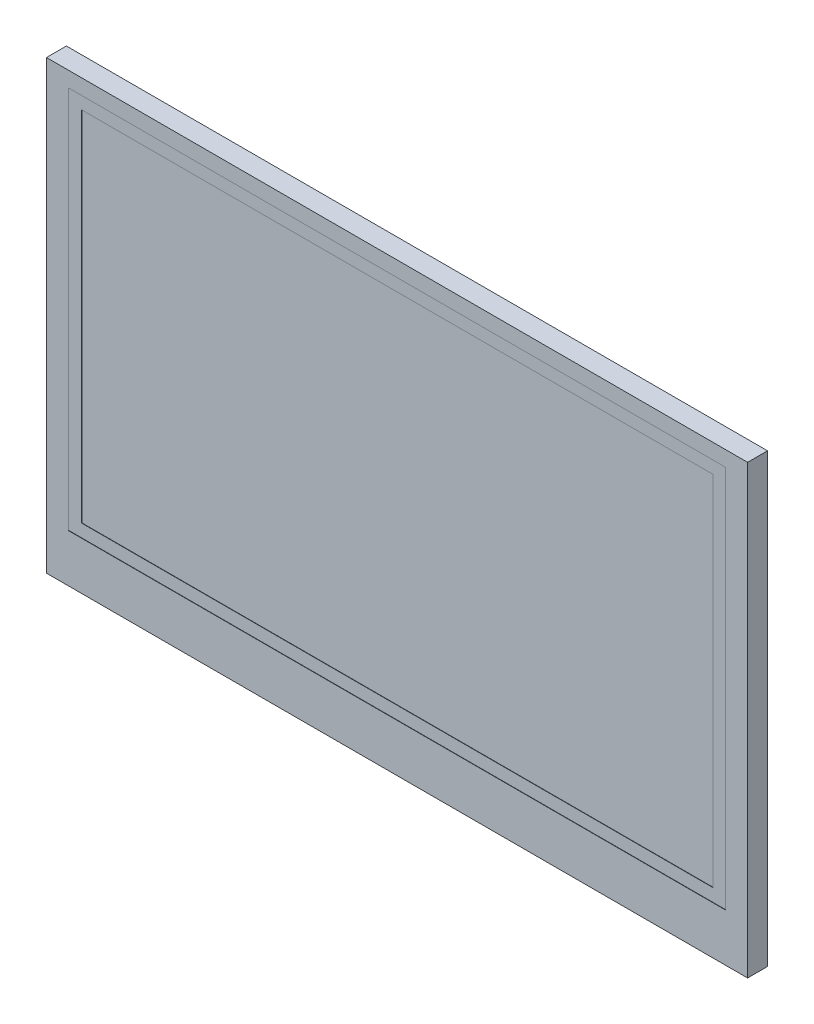
SolidWorks part; units mm, degrees
ref_plane "Front Plane" through (0, 0, 0) normal (0, 0, 1) x (1, 0, 0)
ref_plane "Top Plane" through (0, 0, 0) normal (0, 1, 0) x (1, 0, 0)
ref_plane "Right Plane" through (0, 0, 0) normal (1, 0, 0) x (0, 0, -1)
sketch "Sketch1" plane through (0, 0, 0) normal (0, 0, 1) x (1, 0, 0)
  line L1 (52.75, 33.6) -> (-52.75, 33.6)
  line L2 (52.75, 33.6) -> (52.75, -33.6)
  line L3 (52.75, -33.6) -> (-52.75, -33.6)
  line L4 (-52.75, 33.6) -> (-52.75, -33.6)
  line L5 (52.75, 33.6) -> (-52.75, -33.6) construction
  line L6 (52.75, -33.6) -> (-52.75, 33.6) construction
  line L7 (-49.45, 31.3) -> (49.45, 31.3)
  line L8 (-49.45, 31.3) -> (-49.45, -26.4)
  line L9 (-49.45, -26.4) -> (49.45, -26.4)
  line L10 (49.45, 31.3) -> (49.45, -26.4)
  line L11 (-47.52, 29.38) -> (47.52, 29.38)
  line L12 (-47.52, 29.38) -> (-47.52, -24.476)
  line L13 (-47.52, -24.476) -> (47.52, -24.476)
  line L14 (47.52, 29.38) -> (47.52, -24.476)
  point P0 (0, 0)
  point P14 (-78.1717, 32.4833)
  point P15 (-49.45, 29.7999)
  point P16 (-47.52, 27.1165)
  dimension "D1" = 105.5
  dimension "D2" = 67.2
  dimension "D3" = 57.7
  dimension "D4" = 98.9
  dimension "D5" = 95.04
  dimension "D6" = 53.856
  dimension "D7" = 3.3
  dimension "D8" = 5.23
  dimension "D9" = 2.3
  dimension "D10" = 4.22
extrude "Boss-Extrude1" add sketch "Sketch1" along normal blind 3 contours L1 L4 L3 L2 L7 L10 L9 L8 region at (51.4992, 0, 0)
extrude "Boss-Extrude2" add sketch "Sketch1<3>" along normal blind 2.95 contours L10 L7 L8 L9 L11 L14 L13 L12 region at (0, 30.155, 0)
sketch "Sketch1<3>" plane through (0, 0, 0) normal (0, 0, 1) x (1, 0, 0) same geometry as "Sketch1"
extrude "Boss-Extrude3" add sketch "Sketch1<4>" along normal blind 2.9 contours L14 L11 L12 L13 region at (0, 2.452, 0)
sketch "Sketch1<4>" plane through (0, 0, 0) normal (0, 0, 1) x (1, 0, 0) same geometry as "Sketch1"
